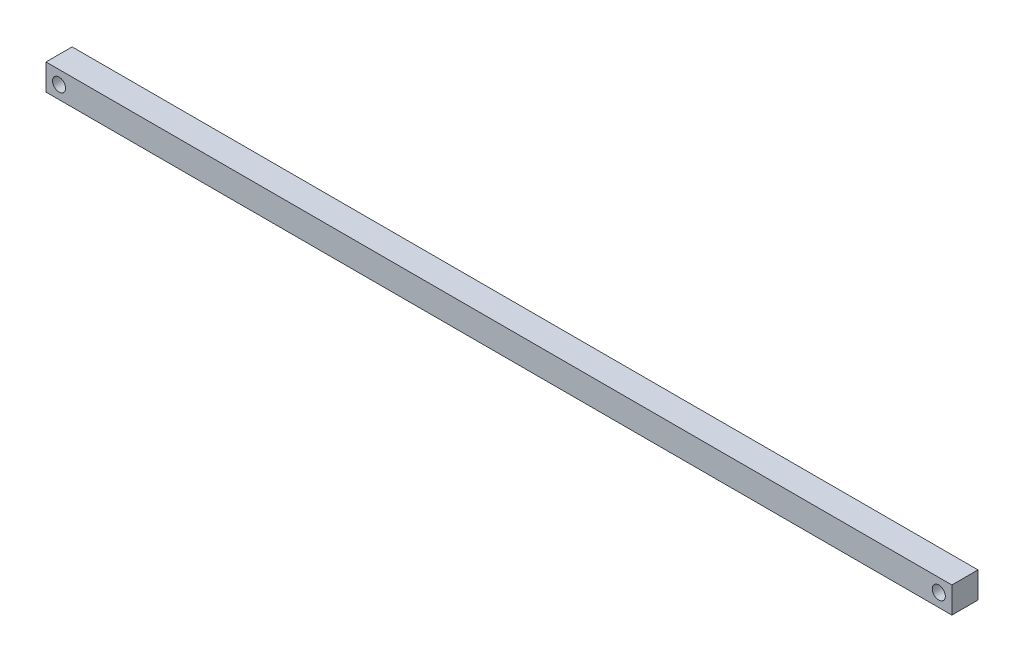
SolidWorks part; units mm, degrees
material "1060 Alloy for 162A"
ref_plane "Front Plane" through (0, 0, 0) normal (0, 0, 1) x (1, 0, 0)
ref_plane "Top Plane" through (0, 0, 0) normal (0, 1, 0) x (1, 0, 0)
ref_plane "Right Plane" through (0, 0, 0) normal (1, 0, 0) x (0, 0, -1)
sketch "Sketch1" plane through (0, 0, 0) normal (0, 0, 1) x (1, 0, 0)
  line L0 (505, 0) -> (-505, 0) construction
  line L1 (520, 15) -> (-520, 15)
  line L2 (520, 15) -> (520, -15)
  line L3 (520, -15) -> (-520, -15)
  line L4 (-520, 15) -> (-520, -15)
  line L5 (520, 15) -> (-520, -15) construction
  line L6 (520, -15) -> (-520, 15) construction
  circle A0 centre (-505, 0) radius 7.5
  circle A1 centre (505, 0) radius 7.5
  point P0 (0, 0)
  point P8 (0, 0)
  dimension "D2" = 15
  dimension "D1" = 30
  dimension "D3" = 1010
  dimension "D4" = 15
extrude "Boss-Extrude1" add sketch "Sketch1" along normal mid plane 30
equation "\"A\"= 202"
equation "\"hole_diameter\"=15"
equation "\"D2@Sketch1\"=\"hole_diameter\""
equation "\"D3@Sketch1\"=5*\"A\""
equation "\"D4@Sketch1\"=\"hole_diameter\""
